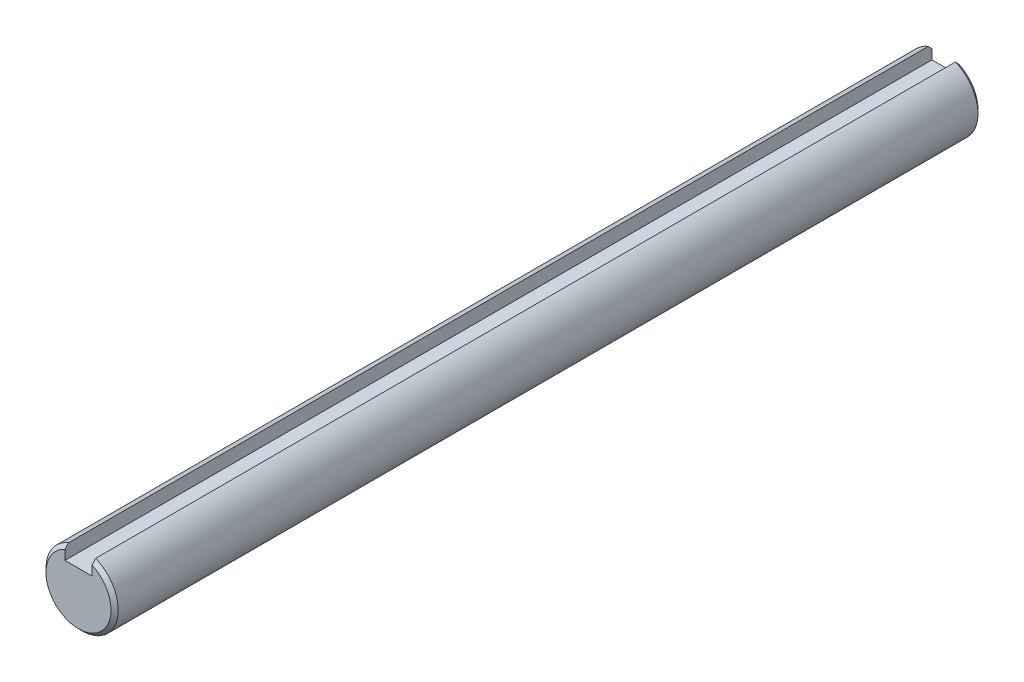
SolidWorks part; units mm, degrees
ref_plane "Front Plane" through (0, 0, 0) normal (0, 0, 1) x (1, 0, 0)
ref_plane "Top Plane" through (0, 0, 0) normal (0, 1, 0) x (1, 0, 0)
ref_plane "Right Plane" through (0, 0, 0) normal (1, 0, 0) x (0, 0, -1)
sketch "Sketch1" plane through (0, 0, 0) normal (0, 0, 1) x (1, 0, 0)
  line L0 (-2.2451, -2.2451) -> (-1.1225, -1.1225) construction
  line L1 (3.4925, 0) -> (-3.4925, 0) construction
  line L2 (0, 0) -> (0, 3.175) construction
  line L4 (-1.1906, 3.175) -> (1.1906, 3.175) construction
  line L5 (-1.1906, 3.175) -> (-1.1906, 1.7527) construction
  line L6 (-1.1906, 1.7527) -> (1.1906, 1.7527) construction
  line L7 (1.1906, 3.175) -> (1.1906, 1.7527) construction
  line L8 (-1.1906, 3.175) -> (1.1906, 1.7527) construction
  line L9 (-1.1906, 1.7527) -> (1.1906, 3.175) construction
  circle A0 centre (0, 0) radius 1.5875 construction
  circle A1 centre (0, 0) radius 3.175 construction
  point P6 (0, 2.4638)
  point P16 (-1.1906, 2.9433)
  dimension "Diameter" = 6.35
  dimension "Thread Dia" = 3.175
  dimension "D1" = 45
  dimension "Keyway Wd" = 2.3813
  dimension "Keyway Ht" = 1.1906
sketch "Sketch2" plane through (0, 0, 0) normal (1, 0, 0) x (0, 0, -1)
  line L0 (-38.1, -3.175) -> (38.1, -3.175) construction
  line L1 (0, 3.175) -> (0, -3.175) construction
  line L2 (0, 3.175) -> (0, -3.175) construction
  point P3 (25.4, -3.175)
  point P4 (-25.4, -3.175)
  dimension "Length" = 76.2
  dimension "D1" = 12.7
  dimension "D2" = 12.7
sketch "Sketch3" plane through (0, 0, 0) normal (0, 0, 1) x (1, 0, 0)
  circle A1 centre (0, 0) radius 3.175 construction
  circle A3 centre (0, 0) radius 3.175
extrude "Boss-Extrude2" add sketch "Sketch3" along normal up to vertex (38.1 mm away) and the other way up to vertex (38.1 mm away) up to point (0, -3.175, 38.1) other way up to point (0, -3.175, -38.1)
sketch "Sketch10" plane through (0, 0, 0) normal (0, 0, 1) x (1, 0, 0)
  line L1 (1.1906, 3.175) -> (1.1906, 1.7527) construction
  line L2 (-1.1906, 1.7527) -> (1.1906, 1.7527) construction
  line L3 (-1.1906, 3.175) -> (-1.1906, 1.7527) construction
  line L4 (-1.1906, 3.175) -> (1.1906, 3.175) construction
  line L5 (1.1906, 3.175) -> (1.1906, 1.7527)
  line L6 (-1.1906, 1.7527) -> (1.1906, 1.7527)
  line L7 (-1.1906, 3.175) -> (-1.1906, 1.7527)
  line L8 (-1.1906, 3.175) -> (1.1906, 3.175)
extrude "Cut-Extrude5" cut sketch "Sketch10" against normal through all both and the other way through all
chamfer "Chamfer1" distance 0.3175 angle 45 2 edges at (0, -3.175, 38.1) (0, -3.175, -38.1)
equation "\"D1@Chamfer1\"= \"Diameter@Sketch1\" / 20"
equation "\"D1@Sketch2\"=\"Diameter@Sketch1\"*2"
equation "\"D2@Sketch2\"=\"D1@Sketch2\""
